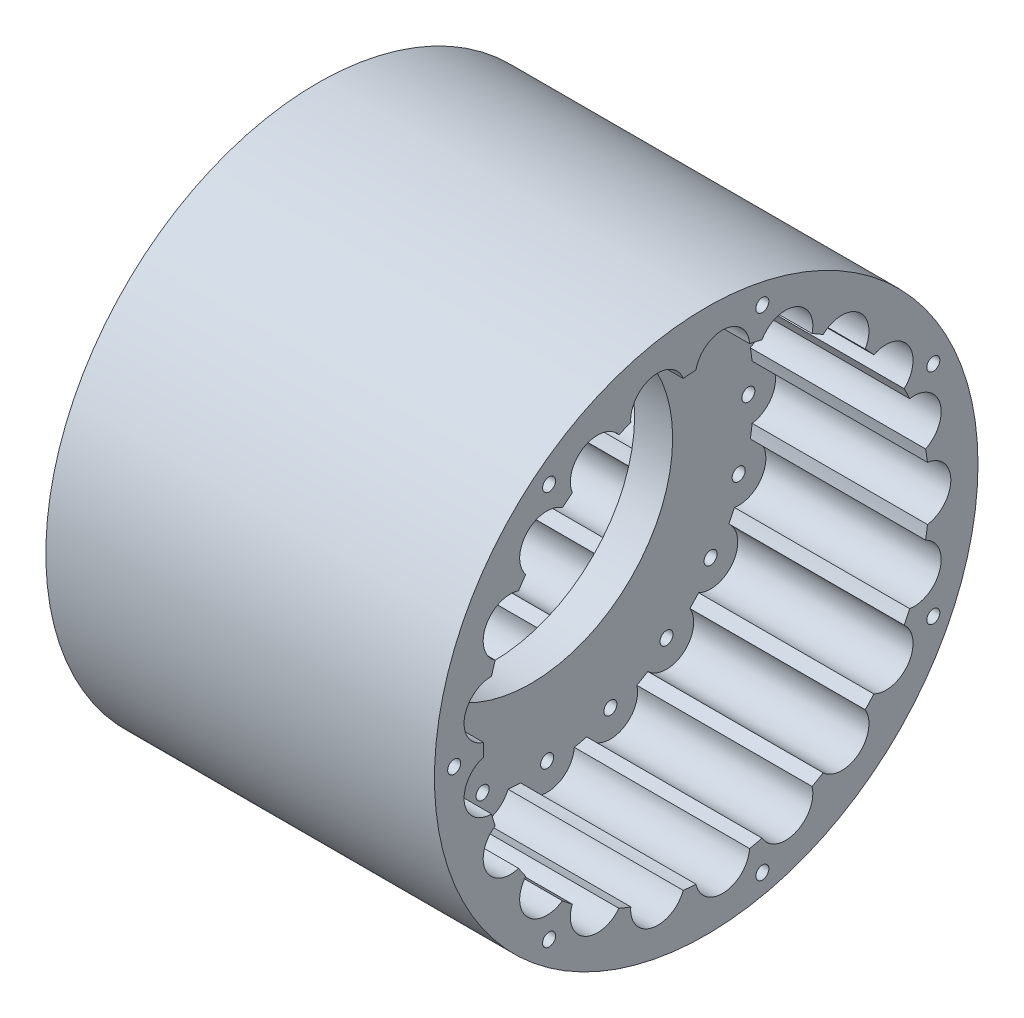
SolidWorks part; units mm, degrees
ref_plane "Ebene vorne" through (0, 0, 0) normal (0, 0, 1) x (1, 0, 0)
ref_plane "Ebene oben" through (0, 0, 0) normal (0, 1, 0) x (1, 0, 0)
ref_plane "Ebene rechts" through (0, 0, 0) normal (1, 0, 0) x (0, 0, -1)
sketch "Skizze2" plane through (0, 0, 0) normal (0, 0, 1) x (1, 0, 0)
  line L0 (0, 0) -> (-33680.1149, 0) construction
  line L1 (0, 26.075) -> (3.5, 26.075)
  line L2 (3.5, 26.075) -> (3.5, 41)
  line L3 (3.5, 41) -> (35.75, 41)
  line L4 (35.75, 41) -> (35.75, 50)
  line L5 (35.75, 50) -> (0, 50)
  line L6 (0, 50) -> (0, 26.075)
  line L7 (0, 0) -> (0, 50000) construction
  dimension "D1" = 52.15
  dimension "D2" = 3.5
  dimension "D3" = 35.75
  dimension "D4" = 100
  dimension "D5" = 82
revolve "Rotation1" add sketch "Skizze2" angle 360 about L0
sketch "Skizze4" plane through (35.75, 0, 0) normal (1, 0, 0) x (0, 0, -1)
  line L0 (0, 0) -> (-50000, 0) construction
  circle A6 centre (0, 0) radius 40 construction
  circle A7 centre (40, 0) radius 5
  circle A8 centre (38.2229, -11.7902) radius 5
  circle A9 centre (33.0496, -22.5328) radius 5
  circle A10 centre (24.9396, -31.2733) radius 5
  circle A11 centre (14.6136, -37.2349) radius 5
  circle A12 centre (2.9892, -39.8882) radius 5
  circle A13 centre (-8.9008, -38.9971) radius 5
  circle A14 centre (-20, -34.641) radius 5
  circle A15 centre (-29.3221, -27.2069) radius 5
  circle A16 centre (-36.0388, -17.3553) radius 5
  circle A17 centre (-39.5532, -5.9617) radius 5
  circle A18 centre (-39.5532, 5.9617) radius 5
  circle A19 centre (-36.0388, 17.3553) radius 5
  circle A20 centre (-29.3221, 27.2069) radius 5
  circle A21 centre (-20, 34.641) radius 5
  circle A22 centre (-8.9008, 38.9971) radius 5
  circle A23 centre (2.9892, 39.8882) radius 5
  circle A24 centre (14.6136, 37.2349) radius 5
  circle A25 centre (24.9396, 31.2733) radius 5
  circle A26 centre (33.0496, 22.5328) radius 5
  circle A27 centre (38.2229, 11.7902) radius 5
  point P49 (0, 0)
  dimension "D2" = 10
  dimension "D3" = 21
extrude "Schnitt-Linear austragen1" cut sketch "Skizze4" against normal up to surface (32.25 mm away) up to face at (3.5, 0, -41)
sketch "Skizze5" plane through (35.75, 0, 0) normal (1, 0, 0) x (0, 0, -1)
  line L0 (0, 0) -> (-50000, 0) construction
  circle A0 centre (-46.3698, 0) radius 1.2
  circle A1 centre (-28.9111, 36.2534) radius 1.2
  circle A2 centre (10.3183, 45.2073) radius 1.2
  circle A3 centre (41.7778, 20.1191) radius 1.2
  circle A4 centre (41.7778, -20.1191) radius 1.2
  circle A5 centre (10.3183, -45.2073) radius 1.2
  circle A6 centre (-28.9111, -36.2534) radius 1.2
  point P20 (0, 0)
  dimension "D1" = 2.4
extrude "Schnitt-Linear austragen2" cut sketch "Skizze5" against normal blind 13
mirror "Spiegeln1" about plane through (0, 0, 0) normal (1, 0, 0) of "Schnitt-Linear austragen2", "Schnitt-Linear austragen1", "Rotation1"
hole_wizard "Ø2.4 (2.4) Durchmesser Bohrung1" positions "Skizze6" profile "Skizze7" hole size "Ø2.4" standard "ISO" end condition through all
sketch "Skizze6" plane through (3.5, 0, 0) normal (1, 0, 0) x (0, 0, -1)
  point P0 (40, 0)
sketch "Skizze7" plane through (3.5, 0, -40) normal (0, 1, 0) x (0, 0, -1)
  line L0 (0, 0) -> (0, 39.25)
  line L1 (0, 39.25) -> (1.2, 39.25)
  line L2 (1.2, 39.25) -> (1.2, 0)
  line L5 (1.2, 0) -> (0, 0)
  line L11 (0, -6.35) -> (0, 107.95) construction
  dimension "Bohrerdurchmesser" = 2.4
  dimension "Bohrungstiefe" = 39.25
pattern_circular "Kreismuster1" count 21 over 360 about axis through (3.5, 0, 0) along (1, 0, 0) of "Ø2.4 (2.4) Durchmesser Bohrung1"
